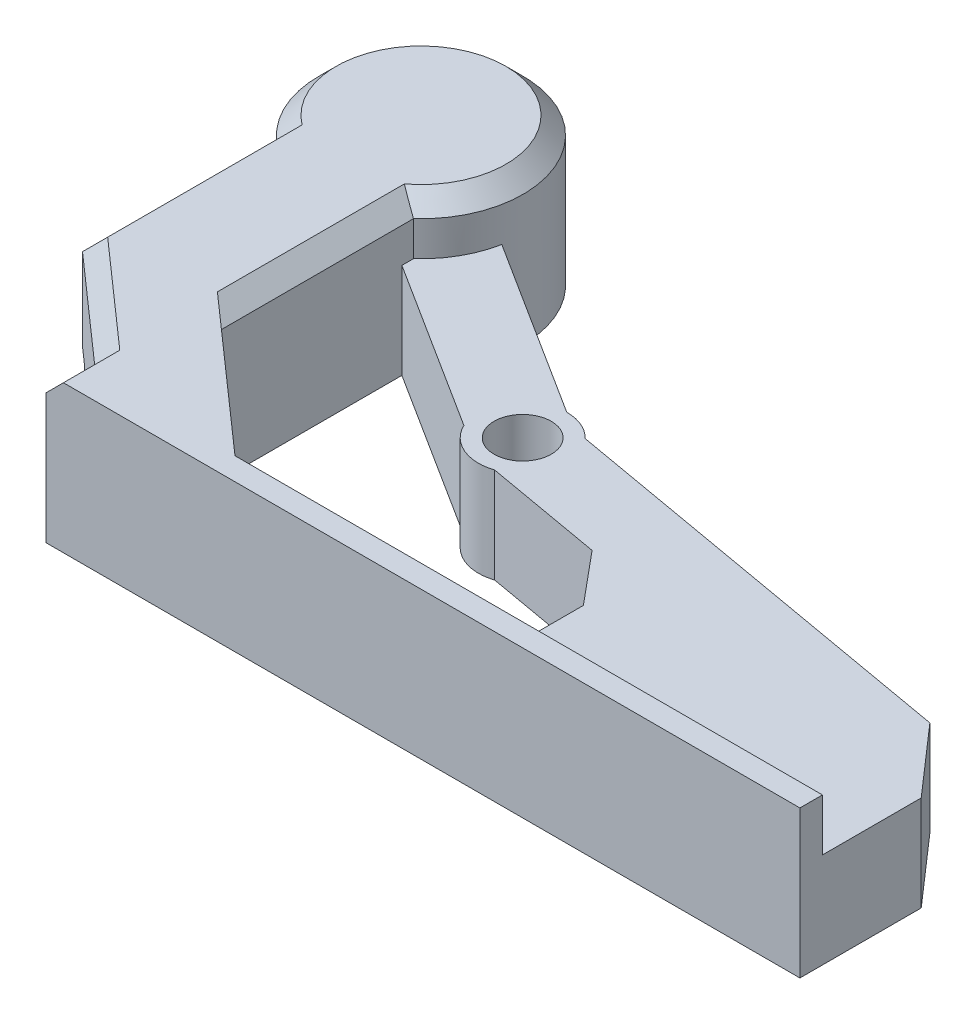
SolidWorks part; units mm, degrees
ref_plane "Front Plane" through (0, 0, 0) normal (0, 0, 1) x (1, 0, 0)
ref_plane "Top Plane" through (0, 0, 0) normal (0, 1, 0) x (1, 0, 0)
ref_plane "Right Plane" through (0, 0, 0) normal (1, 0, 0) x (0, 0, -1)
sketch "Sketch1" plane through (0, 0, 0) normal (0, 1, 0) x (1, 0, 0)
  line L0 (21.75, 0) -> (-21.75, 0)
  line L1 (-21.75, 0) -> (-21.75, 1.3)
  line L2 (-21.75, 1.3) -> (21.75, 1.3)
  line L3 (21.75, 1.3) -> (21.75, 0)
  line L4 (21.75, 0) -> (21.75, 7)
  line L5 (21.75, 7) -> (18.25, 11)
  line L6 (18.25, 11) -> (-7.25, 15.5)
  line L7 (-7.9973, 11.2654) -> (-0.119, 9.8751)
  line L8 (-7.25, 15.5) -> (-7.9973, 11.2654)
  line L9 (-0.119, 9.8751) -> (2.381, 6.8751)
  line L10 (2.381, 6.8751) -> (2.381, 1.3)
  line L11 (-8.9018, 11.6845) -> (-6.5982, 15.3155)
  line L12 (-6.5982, 15.3155) -> (-21.7974, 24.9583)
  line L13 (-21.7974, 24.9583) -> (-24.101, 21.3274)
  line L14 (-24.101, 21.3274) -> (-8.9018, 11.6845)
  line L15 (-7.75, 13.5) -> (-23.8, 23.6826) construction
  line L16 (-21.75, 0) -> (-21.75, 2.8)
  line L17 (-21.75, 2.8) -> (-27.75, 8.1)
  line L18 (-27.75, 8.1) -> (-27.75, 19.3)
  line L19 (-27.75, 19.3) -> (-19.85, 19.3)
  line L20 (-19.85, 19.3) -> (-19.85, 8.1)
  line L21 (-19.85, 8.1) -> (-12.1519, 1.3)
  circle A0 centre (-7.75, 13.5) radius 1.65
  circle A1 centre (-7.75, 13.5) radius 2.55
  circle A2 centre (-23.8, 23.6826) radius 5.9
  point P4 (0, 0)
  dimension "D15" = 3.3
  dimension "D16" = 5.1
  dimension "D25" = 11.8
  dimension "D1" = 1.3
  dimension "D2" = 43.5
  dimension "D3" = 0
  dimension "D4" = 7
  dimension "D5" = 4
  dimension "D6" = 3.5
  dimension "D7" = 29
  dimension "D8" = 15.5
  dimension "D9" = 4.3
  dimension "D10" = 8
  dimension "D11" = 3
  dimension "D12" = 2.5
  dimension "D13" = 29.5
  dimension "D14" = 13.5
  dimension "D17" = 4.3
  dimension "D18" = 18
  dimension "D19" = 2.8
  dimension "D20" = 6
  dimension "D21" = 5.3
  dimension "D22" = 11.2
  dimension "D23" = 7.9
  dimension "D24" = 11.2
extrude "Boss-Extrude1" add sketch "Sketch1" along normal blind 5.5 contours L15 A0 L8 L6 L12 A1 | A0 L11 L12 L6 L8 | L7 A1 L6 L12 L11 A0 L8 | L6 A1 L12 | A0 L15 A1 L14 L11 | L14 A1 L7 L8 A0 L11 | A1 L15 A2 L20 L14 | L14 A2 L19 | A2 L14 L20 | A2 L15 L13 L14 L19 | L15 A2 L12 L13 | L12 A2 L19 L14 L13 | L19 A2 L14 | A2 L18 L17 L16 L2 L21 L20 L14 | L3 L2 L1 L0 | A1 L7 L9 L10 L2 L4 L5 L6 | L15 A1 L12 A2 | A1 region at (0, 0, -0.65) region at (9.2958, 0, -7.5009) region at (-22.2491, 0, -9.6998) region at (-5.4314, 0, -14.4307) region at (-6.8016, 0, -15.6679) region at (-14.8223, 0, -16.6916) region at (-20.0026, 0, -18.9483) region at (-24.5154, 0, -24.6388) region at (-23.8866, 0, -18.6736) region at (-8.5807, 0, -11.5298) region at (-6.9861, 0, -15.2256) region at (-8.5029, 0, -15.3336) region at (-13.6776, 0, -18.5626) region at (-20.3518, 0, -19.1736) region at (-9.6514, 0, -13.2605) region at (-21.5296, 0, -21.0085) region at (-20.3708, 0, -22.7622)
sketch "Sketch2" plane through (0, 5.5, 0) normal (0, 1, 0) x (1, 0, 0)
  circle A0 centre (-7.75, 13.5) radius 1.65
  dimension "D1" = 3.3
extrude "Cut-Extrude1" cut sketch "Sketch2" against normal blind 5.5
sketch "Sketch3" plane through (0, 5.5, 0) normal (0, 1, 0) x (1, 0, 0)
  line L0 (-19.85, 8.1) -> (-19.85, 19.3)
  line L1 (-27.75, 8.1) -> (-27.75, 19.3)
  line L2 (-27.75, 8.1) -> (-21.75, 2.8)
  line L3 (-21.75, 2.8) -> (-21.75, 0)
  line L4 (-21.75, 0) -> (21.75, 0)
  line L5 (21.75, 0) -> (21.75, 1.3)
  line L6 (21.75, 0) -> (21.75, 7) construction
  line L7 (21.75, 1.3) -> (-12.1519, 1.3)
  line L8 (-12.1519, 1.3) -> (-19.85, 8.1)
  circle A0 centre (-23.8, 23.6826) radius 5.9
  line M8 (2.381, 1.3) -> (-12.1519, 1.3)
  line M9 (-12.1519, 1.3) -> (-19.85, 8.1)
  line M10 (-19.85, 8.1) -> (-19.85, 18.6304)
  arc M14 (-18.0088, 22.5547) -> (-27.75, 19.3) centre (-23.8, 23.6826) ccw
  line M15 (-27.75, 19.3) -> (-27.75, 8.1)
  line M16 (-27.75, 8.1) -> (-21.75, 2.8)
  line M17 (-21.75, 2.8) -> (-21.75, 0)
  line M18 (-21.75, 0) -> (21.75, 0)
  line M19 (21.75, 0) -> (21.75, 7)
  dimension "D1" = 11.8
extrude "Boss-Extrude2" add sketch "Sketch3" along normal blind 3 contours A0 M14 | A0 L7 L0 M15 M16 M17 M18 M19 M8 M9 M10 region at (-16.3527, 5.5, -4.3018) region at (-23.8, 5.5, -23.6826)
sketch "Sketch4" plane through (0, 0, 0) normal (0, -1, 0) x (1, 0, 0)
  line L0 (-23.8, -29.5826) -> (-23.8, -7.3)
  line L1 (-23.8, -7.3) -> (-26.8443, -7.3)
  line L2 (-21.75, -2.8) -> (-27.75, -8.1) construction
  line L3 (-26.8443, -7.3) -> (-27.75, -8.1)
  line L4 (-27.75, -8.1) -> (-27.75, -19.3)
  arc A0 (-27.75, -19.3) -> (-18.0088, -22.5547) centre (-23.8, -23.6826) ccw construction
  circle A1 centre (-23.8, -23.6826) radius 5.9
  line M18 (-21.75, -2.8) -> (-27.75, -8.1)
  line M19 (-27.75, -8.1) -> (-27.75, -19.3)
  arc M20 (-27.75, -19.3) -> (-18.0088, -22.5547) centre (-23.8, -23.6826) ccw
  dimension "D2" = 11.8
  dimension "D1" = 0.8
extrude "Cut-Extrude2" cut sketch "Sketch4" against normal offset from surface (2.75 mm away) 5.75 contours L0 A1 M20 | A1 L0 L1 M18 M19 region at (-26.304, 0, -23.6826) region at (-25.8054, 0, -12.8326) up to face at (-11.928, 8.5, -7.8314)
sketch "Sketch5" plane through (0, 0, 0) normal (0, -1, 0) x (1, 0, 0)
  line L0 (21.75, 0) -> (-21.75, 0) construction
  circle A0 centre (-23.8, -23.6826) radius 1.95
  circle A1 centre (-23.8, -13.8826) radius 1.35
  circle A2 centre (-20, -4.3826) radius 1.15
  circle A3 centre (15.0006, -5.5) radius 2
  dimension "D1" = 3.9
  dimension "D3" = 2.7
  dimension "D7" = 2.3
  dimension "D8" = 4
  dimension "D2" = 0
  dimension "D4" = 3.8
  dimension "D5" = 9.5
  dimension "D6" = 9.8
  dimension "D9" = 38.8006
  dimension "D10" = 5.5
extrude "Cut-Extrude3" cut sketch "Sketch5" against normal offset from surface (4.3 mm away) 1.2 up to face at (-1.7017, 5.5, -11.7406)
sketch "Sketch7" plane through (0, 4.3, 0) normal (0, -1, 0) x (1, 0, 0)
  circle A0 centre (-23.8, -13.8826) radius 1.35
  circle A1 centre (-23.8, -23.6826) radius 1.95
  dimension "D1" = 3.9
  dimension "D2" = 2.7
extrude "Cut-Extrude4" cut sketch "Sketch7" against normal offset from surface (3 mm away) 1.2 contours A1 | A0 region at (-23.8, 4.3, -23.6826) up to face at (-11.928, 8.5, -7.8314)
chamfer "Chamfer1" distance 1 angle 45 5 edges at (-21.75, 8.5, -1.4) (-24.75, 8.5, -5.45) (-27.75, 8.5, -13.7) (-19.85, 8.5, -13.7) (-23.8, 8.5, -29.5826)
sketch "Sketch8" plane through (0, 0, 0) normal (0, -1, 0) x (1, 0, 0)
  line L0 (-23.8, -7.3) -> (-21.05, -7.3)
  line L1 (-21.05, -7.3) -> (-21.05, -19.8711)
  line L2 (-19.85, -18.6304) -> (-19.85, -8.1) construction
  line L3 (-23.8, -7.3) -> (-23.8, -18.9826)
  circle A0 centre (-23.8, -23.6826) radius 4.7
  arc A1 (-23.8, -29.5826) -> (-18.0088, -22.5547) centre (-23.8, -23.6826) ccw construction
  line M13 (-23.8, -15.2326) -> (-23.8, -21.7326)
  arc M14 (-23.8, -21.7326) -> (-23.8, -25.6326) centre (-23.8, -23.6826) cw
  line M15 (-23.8, -25.6326) -> (-23.8, -29.5826)
  line M26 (-23.8, -7.3) -> (-23.8, -12.5326)
  arc M27 (-23.8, -12.5326) -> (-23.8, -15.2326) centre (-23.8, -13.8826) cw
  dimension "D1" = 1.2
  dimension "D2" = 1.2
extrude "Cut-Extrude5" cut sketch "Sketch8" against normal up to surface (2.75 mm away) contours A0 L1 L0 M26 M27 M13 | A0 M15 M13 M14 region at (-22.3304, 0, -13.2293) region at (-21.5626, 0, -23.6826) up to face at (-25.7752, 2.75, -16.4522)
